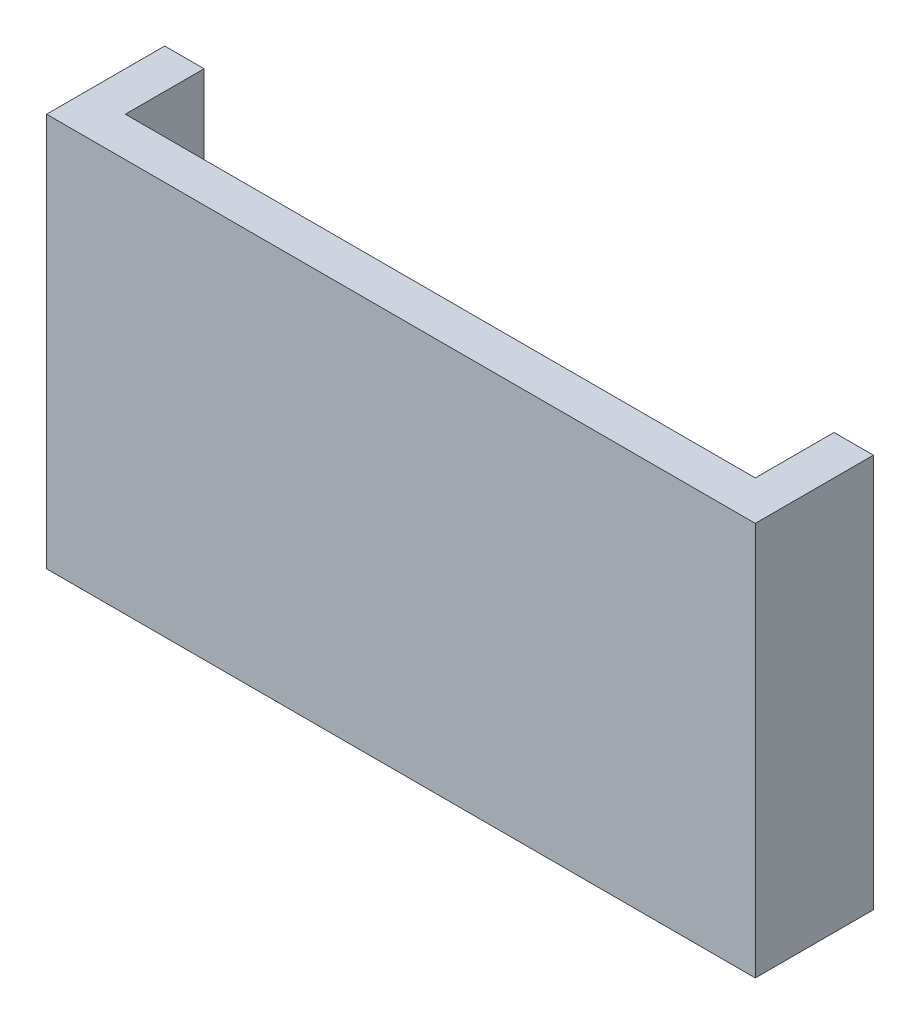
SolidWorks part; units mm, degrees
ref_plane "Front Plane" through (0, 0, 0) normal (0, 0, 1) x (1, 0, 0)
ref_plane "Top Plane" through (0, 0, 0) normal (0, 1, 0) x (1, 0, 0)
ref_plane "Right Plane" through (0, 0, 0) normal (1, 0, 0) x (0, 0, -1)
sketch "Sketch1" plane through (0, 0, 0) normal (0, 1, 0) x (1, 0, 0)
  line L0 (0, 0) -> (-18, 0)
  line L5 (-18, 0) -> (-18, 3)
  line L6 (-18, 3) -> (0, 3)
  line L7 (0, 3) -> (0, 0)
  line L8 (-17, 3) -> (-17, 0)
  line L9 (-1, 3) -> (-1, 0)
  line L10 (-17, 2) -> (-2, 2)
  line L11 (-17, 1) -> (-1, 1)
  line L12 (-2, 2) -> (-2, 3)
  point P0 (0, 0)
  dimension "D1" = 3
  dimension "D2" = 18
  dimension "D3" = 1
  dimension "D4" = 1
  dimension "D5" = 1
  dimension "D6" = 1
  dimension "D7" = 1
extrude "Boss-Extrude1" add sketch "Sketch1" along normal blind 7 contours L10 L12 L6 L8 region at (-9.5, 0, -2.5)
extrude "Boss-Extrude2" add sketch "Sketch1<3>" along normal blind 1 contours L12 L10 L8 L11 L9 L6 region at (-8.5588, 0, -1.5588)
sketch "Sketch1<3>" plane through (0, 0, 0) normal (0, 1, 0) x (1, 0, 0) same geometry as "Sketch1"
extrude "Boss-Extrude4" add sketch "Sketch1<5>" along normal blind 10 contours L8 L6 L5 L0 | L11 L8 L0 L9 | L6 L9 L0 L7 region at (-0.5, 0, -1.5) region at (-9, 0, -0.5) region at (-17.5, 0, -1.5)
sketch "Sketch1<5>" plane through (0, 0, 0) normal (0, 1, 0) x (1, 0, 0) same geometry as "Sketch1"
